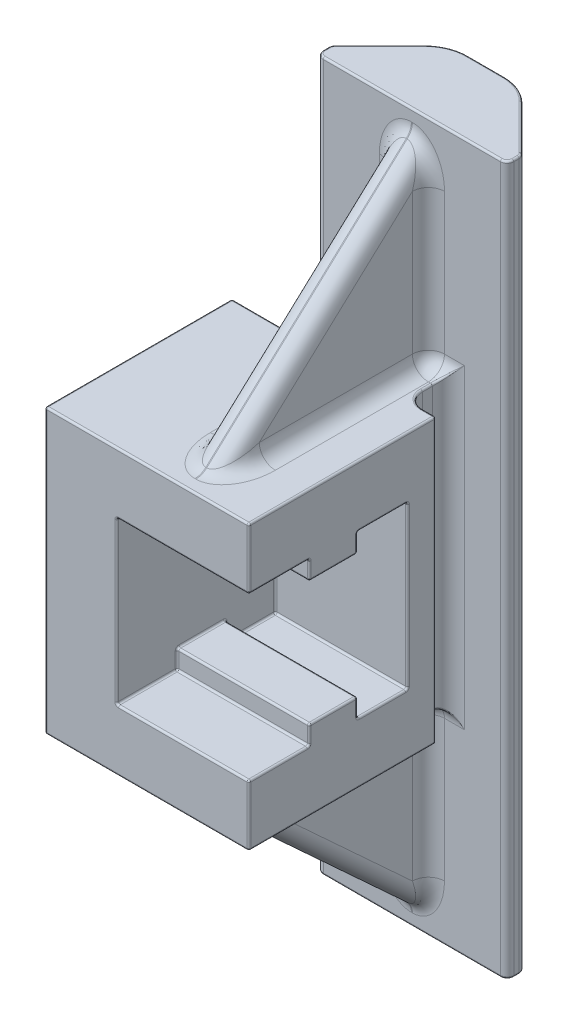
SolidWorks part; units mm, degrees
ref_plane "Front Plane" through (0, 0, 0) normal (0, 0, 1) x (1, 0, 0)
ref_plane "Top Plane" through (0, 0, 0) normal (0, 1, 0) x (1, 0, 0)
ref_plane "Right Plane" through (0, 0, 0) normal (1, 0, 0) x (0, 0, -1)
sketch "Sketch15" plane through (0, 0, 0) normal (0, 1, 0) x (1, 0, 0)
  line L0 (-3.864, 1.5536) -> (-3.864, 2.5104) construction
  line L1 (-5.6176, 4.264) -> (-9.3853, 4.264)
  line L2 (-10.087, 4.9657) -> (-10.087, 5.534)
  line L3 (-9.8815, 6.0301) -> (-5.1506, 10.761)
  line L4 (-1.9335, 12.0936) -> (1.9335, 12.0936)
  line L5 (5.1506, 10.761) -> (9.8815, 6.0301)
  line L6 (10.087, 5.534) -> (10.087, 4.9657)
  line L7 (9.3853, 4.264) -> (5.6176, 4.264)
  line L8 (3.864, 2.5104) -> (3.864, 1.5536) construction
  line L9 (-5.6176, 4.264) -> (5.6176, 4.264)
  line L130 (-14.3277, 0) -> (-9.4961, 0) construction
  line L131 (-7.9763, 0) -> (-5.6176, 0) construction
  line L132 (-4.064, 1.5536) -> (-4.064, 2.5104) construction
  line L133 (-5.6176, 4.064) -> (-9.3853, 4.064) construction
  line L134 (-10.287, 4.9657) -> (-10.287, 5.534) construction
  line L135 (-10.0229, 6.1716) -> (-5.2921, 10.9024) construction
  line L136 (-1.9335, 12.2936) -> (1.9335, 12.2936) construction
  line L137 (5.2921, 10.9024) -> (10.0229, 6.1716) construction
  line L138 (10.287, 5.534) -> (10.287, 4.9657) construction
  line L139 (9.3853, 4.064) -> (5.6176, 4.064) construction
  line L140 (4.064, 2.5104) -> (4.064, 1.5536) construction
  line L141 (5.6176, 0) -> (7.9763, 0) construction
  line L142 (9.4961, 0) -> (14.3277, 0) construction
  arc A0 (-5.6176, -0.2) -> (-3.864, 1.5536) centre (-5.6176, 1.5536) ccw construction
  arc A1 (-3.864, 2.5104) -> (-5.6176, 4.264) centre (-5.6176, 2.5104) ccw construction
  arc A2 (-10.087, 4.9657) -> (-9.3853, 4.264) centre (-9.3853, 4.9657) ccw
  arc A3 (-9.8815, 6.0301) -> (-10.087, 5.534) centre (-9.3853, 5.534) ccw
  arc A4 (-1.9335, 12.0936) -> (-5.1506, 10.761) centre (-1.9335, 7.5438) ccw
  arc A5 (5.1506, 10.761) -> (1.9335, 12.0936) centre (1.9335, 7.5438) ccw
  arc A6 (10.087, 5.534) -> (9.8815, 6.0301) centre (9.3853, 5.534) ccw
  arc A7 (9.3853, 4.264) -> (10.087, 4.9657) centre (9.3853, 4.9657) ccw
  arc A8 (5.6176, 4.264) -> (3.864, 2.5104) centre (5.6176, 2.5104) ccw construction
  arc A9 (3.864, 1.5536) -> (5.6176, -0.2) centre (5.6176, 1.5536) ccw construction
  arc A151 (-19.05, 3.2025) -> (-15.8475, 0) centre (-15.8751, 3.1749) ccw construction
  arc A152 (-14.3277, 0) -> (-15.8475, 0) centre (-15.0876, 0.0567) ccw construction
  arc A153 (-7.9763, 0) -> (-9.4961, 0) centre (-8.7362, 0.0567) ccw construction
  arc A154 (-5.6176, 0) -> (-4.064, 1.5536) centre (-5.6176, 1.5536) ccw construction
  arc A155 (-4.064, 2.5104) -> (-5.6176, 4.064) centre (-5.6176, 2.5104) ccw construction
  arc A156 (-10.287, 4.9657) -> (-9.3853, 4.064) centre (-9.3853, 4.9657) ccw construction
  arc A157 (-10.0229, 6.1716) -> (-10.287, 5.534) centre (-9.3853, 5.534) ccw construction
  arc A158 (-1.9335, 12.2936) -> (-5.2921, 10.9024) centre (-1.9335, 7.5438) ccw construction
  arc A159 (5.2921, 10.9024) -> (1.9335, 12.2936) centre (1.9335, 7.5438) ccw construction
  arc A160 (10.287, 5.534) -> (10.0229, 6.1716) centre (9.3853, 5.534) ccw construction
  arc A161 (9.3853, 4.064) -> (10.287, 4.9657) centre (9.3853, 4.9657) ccw construction
  arc A162 (5.6176, 4.064) -> (4.064, 2.5104) centre (5.6176, 2.5104) ccw construction
  arc A163 (4.064, 1.5536) -> (5.6176, 0) centre (5.6176, 1.5536) ccw construction
  arc A164 (9.4961, 0) -> (7.9763, 0) centre (8.7362, 0.0567) ccw construction
  point P0 (11.9119, 0)
  dimension "D1" = 0.2
extrude "Boss-Extrude6" add sketch "Sketch15" along normal mid plane 75
sketch "Sketch1" plane through (0, 0, 0) normal (0, 1, 0) x (1, 0, 0)
  line L0 (-14.5877, -0.2) -> (-14.5877, -20)
  line L5 (7, -0.2) -> (7, -20)
  line L6 (5.6176, -0.2) -> (8.2363, -0.2) construction
  line L7 (-14.5877, -20) -> (7, -20)
  line L8 (-5.6176, -0.2) -> (-3.864, -0.2)
  line L9 (-3.864, -0.2) -> (-3.864, 1.5536)
  line L10 (-3.864, 2.5104) -> (-3.864, 5)
  line L11 (3.864, 1.5536) -> (3.864, -0.2)
  line L12 (3.864, 2.5104) -> (3.864, 5)
  line L13 (3.864, -0.2) -> (5.6176, -0.2)
  line L14 (-14.3277, 0) -> (-9.4961, 0) construction
  line L16 (5.6176, 0) -> (7.9763, 0) construction
  line L17 (4.064, 2.5104) -> (4.064, 1.5536) construction
  line L18 (9.3853, 4.064) -> (5.6176, 4.064) construction
  line L19 (-7.9763, 0) -> (-5.6176, 0) construction
  line L20 (-4.064, 1.5536) -> (-4.064, 2.5104) construction
  line L21 (-5.6176, 4.064) -> (-9.3853, 4.064) construction
  line L22 (-14.5877, -0.2) -> (-9.2361, -0.2)
  line L23 (-8.2363, -0.2) -> (-5.6176, -0.2)
  line L24 (-3.864, 1.5536) -> (-3.864, 2.5104)
  line L27 (3.864, 2.5104) -> (3.864, 1.5536)
  line L28 (5.6176, -0.2) -> (7, -0.2)
  line L30 (9.3853, 4.264) -> (5.6176, 4.264) construction
  line L31 (-5.6176, 4.264) -> (-9.3853, 4.264) construction
  line L32 (3.864, 5) -> (-3.864, 5)
  line L35 (9.2361, -0.2) -> (14.5877, -0.2) construction
  line L36 (9.4961, 0) -> (14.3277, 0) construction
  arc A0 (-8.2363, -0.2) -> (-9.2361, -0.2) centre (-8.7362, -0.2) ccw
  arc A10 (-19.05, 3.2025) -> (-15.8475, 0) centre (-15.8751, 3.1749) ccw construction
  arc A11 (-14.3277, 0) -> (-15.8475, 0) centre (-15.0876, 0.0567) ccw construction
  arc A12 (-7.9763, 0) -> (-9.4961, 0) centre (-8.7362, 0.0567) ccw construction
  arc A15 (9.4961, 0) -> (7.9763, 0) centre (8.7362, 0.0567) ccw construction
  arc A16 (4.064, 1.5536) -> (5.6176, 0) centre (5.6176, 1.5536) ccw construction
  arc A17 (5.6176, 4.064) -> (4.064, 2.5104) centre (5.6176, 2.5104) ccw construction
  arc A18 (-5.6176, 0) -> (-4.064, 1.5536) centre (-5.6176, 1.5536) ccw construction
  arc A19 (-4.064, 2.5104) -> (-5.6176, 4.064) centre (-5.6176, 2.5104) ccw construction
  arc A23 (-5.6176, -0.2) -> (-3.864, 1.5536) centre (-5.6176, 1.5536) ccw construction
  arc A24 (-3.864, 2.5104) -> (-5.6176, 4.264) centre (-5.6176, 2.5104) ccw construction
  arc A25 (5.6176, 4.264) -> (3.864, 2.5104) centre (5.6176, 2.5104) ccw construction
  arc A26 (3.864, 1.5536) -> (5.6176, -0.2) centre (5.6176, 1.5536) ccw construction
  arc A30 (15.5934, -0.1883) -> (14.5877, -0.2) centre (15.0876, 0.0567) ccw construction
  arc A31 (15.5934, -0.1883) -> (19.25, 3.2043) centre (15.8751, 3.1749) ccw construction
  arc A32 (15.8475, 0) -> (19.05, 3.2025) centre (15.8751, 3.1749) ccw construction
  arc A33 (15.8475, 0) -> (14.3277, 0) centre (15.0876, 0.0567) ccw construction
  arc A34 (-19.25, 3.2043) -> (-15.5934, -0.1883) centre (-15.8751, 3.1749) ccw construction
  arc A35 (-14.5877, -0.2) -> (-15.5934, -0.1883) centre (-15.0876, 0.0567) ccw construction
  arc A36 (-8.2363, -0.2) -> (-9.2361, -0.2) centre (-8.7362, 0.0567) ccw construction
  arc A37 (9.2361, -0.2) -> (8.2363, -0.2) centre (8.7362, 0.0567) ccw construction
  point P0 (0, 0)
  dimension "D1" = 5
  dimension "D2" = 20
  dimension "D4" = 7
  dimension "D3" = 0.2
extrude "Boss-Extrude1" add sketch "Sketch1" along normal mid plane 30
sketch "Sketch12" plane through (7, 0, 0) normal (1, 0, 0) x (0, 0, -1)
  line L0 (-22.6, 8.55) -> (-22.6, -8.55)
  line L2 (-22.6, 8.55) -> (-13.6, 8.55)
  line L3 (-13.6, 8.55) -> (-13.6, 6.55)
  line L4 (-13.6, 6.55) -> (-8.5, 6.55)
  line L5 (-8.5, 6.55) -> (-8.5, 8.55)
  line L6 (-8.5, 8.55) -> (-3.2, 8.55)
  line L7 (-3.2, 8.55) -> (-3.2, -8.55)
  line L8 (-3.2, -8.55) -> (-8.5, -8.55)
  line L9 (-8.5, -8.55) -> (-8.5, -6.55)
  line L10 (-8.5, -6.55) -> (-13.6, -6.55)
  line L11 (-13.6, -6.55) -> (-13.6, -8.55)
  line L12 (-13.6, -8.55) -> (-22.6, -8.55)
  line L13 (-0.2, 0) -> (-22.6, 0) construction
  line L14 (-0.2, 15) -> (-0.2, -15) construction
  point P5 (-22.6, 0)
  dimension "D1" = 17.1
  dimension "D2" = 9
  dimension "D3" = 5.1
  dimension "D4" = 5.3
  dimension "D5" = 2
  dimension "D6" = 3.2
extrude "Cut-Extrude4" cut sketch "Sketch12" against normal blind 14
sketch "Sketch16" plane through (0, 0, 0) normal (1, 0, 0) x (0, 0, -1)
  line L0 (4.264, 37.5) -> (4.264, -37.5) construction
  line L1 (-0.2, 15) -> (4.264, 15) construction
  line L2 (-20, 15) -> (-0.2, 15) construction
  line L3 (4.264, 37.5) -> (4.264, -37.5) construction
  line L4 (-0.2, 15) -> (4.264, 15) construction
  line L5 (-20, 15) -> (-0.2, 15) construction
  line L6 (-18, 15) -> (4.264, 35.5)
  dimension "D1" = 2
  dimension "D2" = 2
rib "Rib1" sketch "Sketch16" sketch "Sketch16" thickness 3.5 extrusion direction parallel to sketch draft on no parameters "D1"=3.5
mirror "Mirror1" about plane through (0, 0, 0) normal (0, 1, 0) of "Rib1"
fillet "Fillet1" radius 1.7 24 edges at (0, -15, 18) (0, -35.5, -4.264) (-1.75, 15, 6.868) (1.75, -25.25, 6.868) (1.75, -15, 6.868) (1.75, -25.25, -4.264) (-1.75, -25.25, 6.868) (-1.75, -25.25, -4.264) (-1.75, -15, 6.868) (2.807, -15, -4.264) (-2.807, -15, -4.264) (-1.75, 25.25, 6.868) (1.75, 25.25, 6.868) (0, 15, 18) (1.75, 25.25, -4.264) (1.75, 15, 6.868) (2.807, 15, -4.264) (3.864, 0, -4.264) (3.864, 0, 0.2) (-3.864, 0, 0.2) (0, 35.5, -4.264) (-1.75, 25.25, -4.264) (-2.807, 15, -4.264) (-3.864, 0, -4.264)
fillet "Fillet2" radius 0.2 91 edges at (-8.7362, 15, -0.2999) (-8.7362, -15, -0.2999) (6.282, 15, 0.2) (4.3619, 15, -0.2979) (3.864, 15, -2.032) (4.3619, -15.4979, -3.7661) (3.864, -15, -2.032) (6.282, -15, 0.2) (-4.3619, 15.4979, -3.7661) (-3.864, 15, -2.032) (-6.9001, 15, 0.2) (-4.3619, -15.4979, -3.7661) (-3.864, -15, -2.032) (-4.3619, -15, -0.2979) (-7.5161, -37.5, -8.3956) (-10.0336, -37.5, -5.8025) (-10.087, -37.5, -5.2498) (-9.8815, -37.5, -4.4695) (0, -37.5, -4.264) (9.8815, -37.5, -4.4695) (10.087, -37.5, -5.2498) (10.0336, -37.5, -5.8025) (7.5161, -37.5, -8.3956) (3.6746, -37.5, -11.7473) (0, -37.5, -12.0936) (-3.6746, -37.5, -11.7473) (3.6746, 37.5, -11.7473) (7.5161, 37.5, -8.3956) (10.0336, 37.5, -5.8025) (10.087, 37.5, -5.2498) (9.8815, 37.5, -4.4695) (0, 37.5, -4.264) (-9.8815, 37.5, -4.4695) (-10.087, 37.5, -5.2498) (-10.0336, 37.5, -5.8025) (-7.5161, 37.5, -8.3956) (-3.6746, 37.5, -11.7473) (0, 37.5, -12.0936) (-9.2361, 0, 0.2) (-11.9119, 15, 0.2) (-11.9119, -15, 0.2) (-14.5877, 0, 0.2) (-14.5877, 15, 10.1) (-14.5877, -15, 10.1) (-3.7939, -15, 20) (-14.5877, 0, 20) (-3.7939, 15, 20) (7, -7.55, 8.5) (7, 8.55, 5.85) (7, 7.55, 8.5) (7, 11.775, 20) (7, 15, 10.1) (7, 0, 0.2) (7, -15, 10.1) (7, -11.775, 20) (7, -7.55, 13.6) (0, -8.55, 20) (0, -8.55, 13.6) (7, -8.55, 16.8) (0, -6.55, 13.6) (0, -6.55, 8.5) (7, -6.55, 11.05) (0, -8.55, 8.5) (7, -8.55, 5.85) (0, -8.55, 3.2) (0, 8.55, 3.2) (7, 0, 3.2) (0, 6.55, 8.5) (7, 6.55, 11.05) (0, 6.55, 13.6) (7, 7.55, 13.6) (0, 8.55, 13.6) (0, 8.55, 20) (7, 8.55, 16.8) (-7, 0, 20) (-7, 8.55, 16.8) (-7, 7.55, 13.6) (-7, 6.55, 11.05) (-7, 7.55, 8.5) (-7, 8.55, 5.85) (-7, 0, 3.2) (-7, -8.55, 5.85) (-7, -7.55, 8.5) (-7, -6.55, 11.05) (-7, -7.55, 13.6) (-7, -8.55, 16.8) (4.3619, 15.4979, -3.7661) (4.3619, -15, -0.2979) (-4.3619, 15, -0.2979) (-6.9001, -15, 0.2) (0, 8.55, 8.5)
